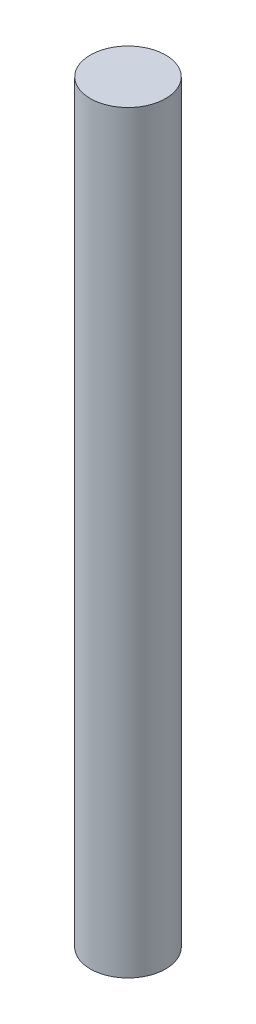
SolidWorks part; units mm, degrees
ref_plane "Front Plane" through (0, 0, 0) normal (0, 0, 1) x (1, 0, 0)
ref_plane "Top Plane" through (0, 0, 0) normal (0, 1, 0) x (1, 0, 0)
ref_plane "Right Plane" through (0, 0, 0) normal (1, 0, 0) x (0, 0, -1)
sketch "Sketch1" plane through (0, 0, 0) normal (0, 1, 0) x (1, 0, 0)
  circle A0 centre (0, 0) radius 5
  dimension "D1" = 10
extrude "Boss-Extrude1" add sketch "Sketch1" along normal blind 100
